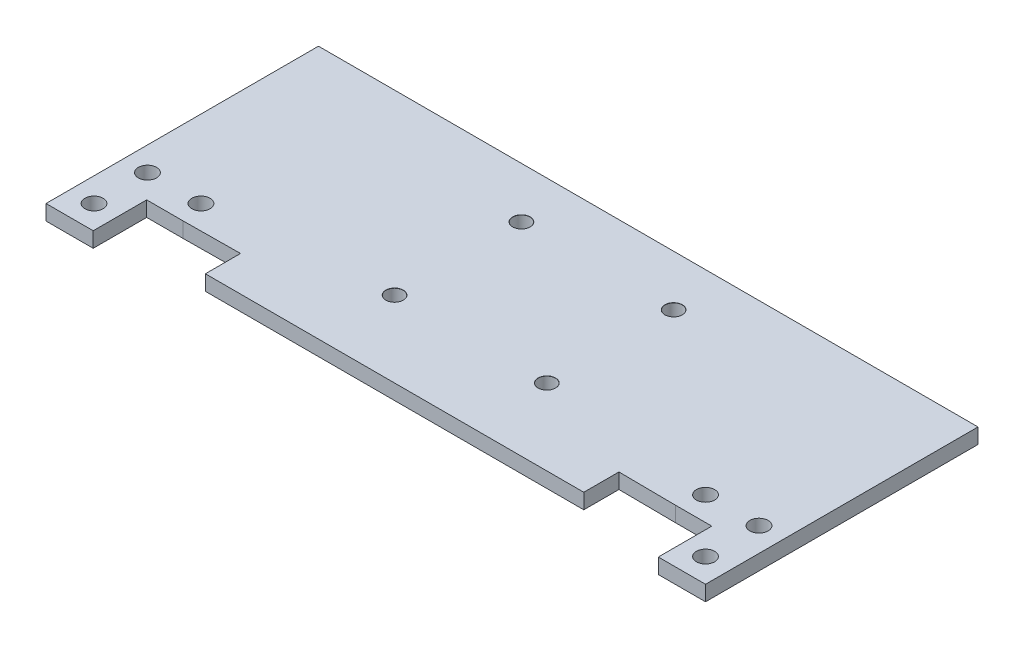
SolidWorks part; units mm, degrees
ref_plane "Front Plane" through (0, 0, 0) normal (0, 0, 1) x (1, 0, 0)
ref_plane "Top Plane" through (0, 0, 0) normal (0, 1, 0) x (1, 0, 0)
ref_plane "Right Plane" through (0, 0, 0) normal (1, 0, 0) x (0, 0, -1)
sketch "Sketch1" plane through (0, 0, 0) normal (1, 0, 0) x (0, 0, -1)
  line L2 (3.71, 3) -> (53.71, 3)
  line L6 (3.71, 0) -> (53.71, 0)
  line L7 (53.71, 0) -> (53.71, 3)
  line L8 (3.71, 3) -> (3.71, 0)
  point P0 (0, 0)
  dimension "D1" = 3.71
  dimension "D3" = 50
  dimension "D6" = 3
extrude "Boss-Extrude1" add sketch "Sketch1" along normal blind 130
hole_wizard "M3 Clearance Hole2" positions "Sketch5" profile "Sketch6" hole size "M3" standard "ANSI Metric" end condition through all
sketch "Sketch5" plane through (0, 3, 0) normal (0, 1, 0) x (1, 0, 0)
  line L0 (65, 53.71) -> (65, 43.71) construction
  line L1 (130, 53.71) -> (0, 53.71) construction
  line L3 (50, 43.71) -> (80, 43.71) construction
  line L4 (80, 43.71) -> (80, 18.71) construction
  line L5 (80, 18.71) -> (50, 18.71) construction
  line L6 (50, 18.71) -> (50, 43.71) construction
  point P9 (50, 43.71)
  point P11 (80, 43.71)
  point P13 (50, 18.71)
  point P15 (80, 18.71)
  point P25 (65, 43.71)
  dimension "D1" = 30
  dimension "D2" = 25
  dimension "D3" = 10
sketch "Sketch6" plane through (80, 3, -18.71) normal (1, 0, 0) x (0, 0, 1)
  line L0 (0, 0) -> (0, 3)
  line L1 (0, 3) -> (1.7, 3)
  line L2 (1.7, 3) -> (1.7, 0.025)
  line L3 (1.7, 0.025) -> (1.725, 0)
  line L5 (1.725, 0) -> (0, 0)
  line L6 (-1.7, 0.025) -> (-1.725, 0) construction
  line L11 (0, -6.35) -> (0, 107.95) construction
  dimension "Thru Hole Dia." = 3.4
  dimension "Thru Hole Depth" = 3
  dimension "Near C'Sink Dia." = 3.45
  dimension "Near C'Sink Angle" = 90
sketch "Sketch7" plane through (0, 0, 0) normal (0, -1, 0) x (1, 0, 0)
  line L0 (130, -3.71) -> (0, -3.71) construction
  line L1 (130, -3.71) -> (0, -3.71)
  line L2 (108.1956, -3.71) -> (108.1956, 0.0001)
  line L3 (108.1956, 0.0001) -> (130, 0.0001)
  line L4 (130, 13.0001) -> (130, -19.9999) construction
  line L5 (130, 0.0001) -> (130, -3.71)
  line L6 (125.2699, -4.73) -> (130, -4.73) construction
  line L7 (130, -3.71) -> (130, -53.71) construction
  line L8 (119.0978, 0.0001) -> (119.0978, -4.73) construction
  line L9 (120.4956, -10.3397) -> (120.4956, 4.3493) construction
  line L10 (120.4956, -10.3397) -> (120.4956, 4.3493) construction
  line L11 (65, -3.71) -> (65, -53.71) construction
  line L12 (130, -53.71) -> (0, -53.71) construction
  line L13 (0, 0.0001) -> (0, -3.71)
  line L14 (21.8044, 0.0001) -> (0, 0.0001)
  line L15 (21.8044, -3.71) -> (21.8044, 0.0001)
  circle A0 centre (125.2699, -4.73) radius 1.8 construction
  circle A1 centre (125.2699, -4.73) radius 1.8 construction
  point P25 (0, 3.7101)
  line M17 (130, -3.71) -> (0, -3.71)
  dimension "D1" = 12.3
extrude "Boss-Extrude2" add sketch "Sketch7" against normal up to surface (3 mm away) contours L5 L3 L2 M17 | L15 L14 L13 M17 region at (10.9022, 0, -1.8549) region at (119.0978, 0, -1.8549) up to face at (50, 3, -41.985)
sketch "Sketch9" plane through (0, 3, 0) normal (0, 1, 0) x (1, 0, 0)
  line L0 (120.4956, 10.3397) -> (113.4956, 10.3397) construction
  line L1 (120.4956, 10.3397) -> (120.4956, -4.3493) construction
  line L2 (120.4956, 10.3397) -> (113.4956, 10.3397)
  line L3 (120.4956, 10.3397) -> (120.4956, -4.3493)
  line L4 (102.4956, 0.9897) -> (102.4956, 10.4376) construction
  line L5 (102.4956, 0.9897) -> (102.4956, 10.4376)
  line L6 (113.4956, 10.3397) -> (102.4956, 10.4376)
  line L7 (102.4956, 0.9897) -> (120.4956, -4.3493)
  line L8 (102.2956, 0.8404) -> (102.2956, 10.6394)
  line L9 (113.4965, 10.5397) -> (102.2956, 10.6394)
  line L10 (120.6956, 10.5397) -> (113.4965, 10.5397)
  line L11 (120.6956, 10.5397) -> (120.6956, -4.6173)
  line L12 (102.2956, 0.8404) -> (120.6956, -4.6173)
  line L13 (108.1956, 3.71) -> (21.8044, 3.71) construction
  line L14 (130, 53.71) -> (0, 53.71) construction
  line L15 (108.1956, 3.71) -> (21.8044, 3.71) construction
  line L16 (130, 53.71) -> (0, 53.71) construction
  line L17 (65, 53.71) -> (65, 3.71) construction
  line L18 (9.3044, 10.5397) -> (9.3044, -4.6173)
  line L19 (9.3044, 10.5397) -> (16.5035, 10.5397)
  line L20 (16.5035, 10.5397) -> (27.7044, 10.6394)
  line L21 (27.7044, 0.8404) -> (27.7044, 10.6394)
  line L22 (27.7044, 0.8404) -> (9.3044, -4.6173)
  line M8 (21.8044, -0.0001) -> (21.8044, 3.71)
  line M9 (21.8044, 3.71) -> (108.1956, 3.71)
  line M10 (108.1956, 3.71) -> (108.1956, -0.0001)
  dimension "D1" = 0.2
extrude "Cut-Extrude1" cut sketch "Sketch9" against normal through all contours L2 L6 L5 L3 M9 | L5 L7 L3 M9 | L8 L12 L11 L3 L7 L5 M10 M9 | L11 L10 L9 L8 L5 L6 L2 L3 M9 | L21 L20 L19 L18 M9 | L22 L21 L18 M9 M8 region at (112.147, 3, -4.2464) region at (102.3195, 3, -7.1747) region at (17.846, 3, -4.2412)
sketch "Sketch10" plane through (0, 3, 0) normal (0, 1, 0) x (1, 0, 0)
  point P0 (125.2699, 4.73)
  point P3 (125.2699, 15.2698)
  point P6 (114.7301, 15.2698)
hole_wizard "M3 Clearance Hole3" positions "Sketch10" profile "Sketch11" hole size "M3" standard "ANSI Metric" end condition through all
sketch "Sketch11" plane through (125.2699, 3, -4.73) normal (1, 0, 0) x (0, 0, 1)
  line L0 (0, 0) -> (0, 3)
  line L1 (0, 3) -> (1.8, 3)
  line L2 (1.8, 3) -> (1.8, 0)
  line L5 (1.8, 0) -> (0, 0)
  line L11 (0, -6.35) -> (0, 107.95) construction
  dimension "Thru Hole Dia." = 3.6
  dimension "Thru Hole Depth" = 3
ref_plane "Plane1" through (65, 0, 0) normal (1, 0, 0) x (0, 0, -1)
mirror "Mirror1" about plane through (65, 0, 0) normal (1, 0, 0) of "M3 Clearance Hole3"
